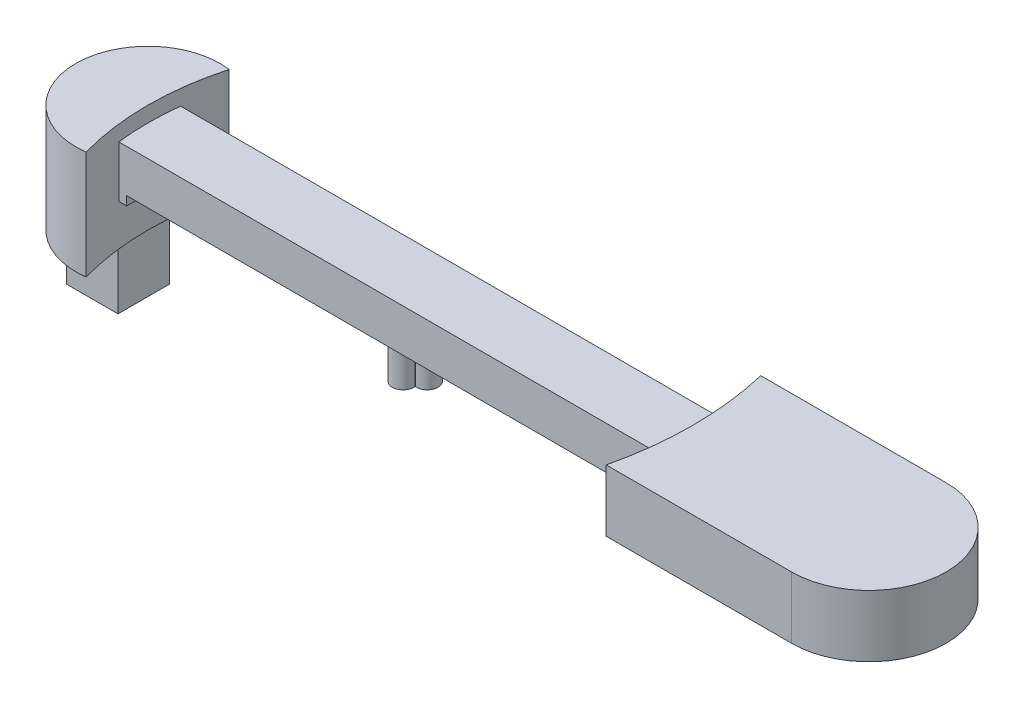
SolidWorks part; units mm, degrees
material "ABS"
ref_plane "Front Plane" through (0, 0, 0) normal (0, 0, 1) x (1, 0, 0)
ref_plane "Top Plane" through (0, 0, 0) normal (0, 1, 0) x (1, 0, 0)
ref_plane "Right Plane" through (0, 0, 0) normal (1, 0, 0) x (0, 0, -1)
sketch "Sketch1" plane through (0, 0, 0) normal (0, 1, 0) x (1, 0, 0)
  line L0 (0, -2241.9542) -> (0, 109855.7559) construction
  line L1 (0, 37.5) -> (90, 37.5)
  line L2 (0, -37.5) -> (90, -37.5)
  line L3 (-1077.9268, 34.7) -> (48922.0732, 34.7) construction
  line L4 (-1075.7317, -34.7) -> (48924.2683, -34.7) construction
  line L5 (0, 0) -> (-255.2, 0) construction
  line L6 (-263.8484, 15) -> (3.7007, 15)
  line L7 (-263.8484, -15) -> (3.7007, -15)
  arc A0 (90, -37.5) -> (90, 37.5) centre (90, 0) ccw
  arc A1 (0, -37.5) -> (0, 37.5) centre (-157.7468, 0) ccw
  arc A9 (-255.2, -34.7) -> (-255.2, 34.7) centre (-129.9167, 0) cw
  arc A10 (-255.2, 34.7) -> (-255.2, -34.7) centre (-259.9167, 0) ccw
  dimension "D8" = 130
  dimension "D9" = 15
  dimension "D1" = 90
  dimension "D2" = 90
  dimension "D3" = 37.5
  dimension "D4" = 37.5
  dimension "D5" = 34.7
  dimension "D6" = 34.7
  dimension "D7" = 255.2
  dimension "D10" = 15
extrude "Boss-Extrude1" add sketch "Sketch1" along normal blind 32.5 and the other way blind 20 contours A9 A10 region at (-273.8974, 0, 0)
extrude "Boss-Extrude2" add sketch "Sketch1<3>" along normal blind 30 separate body contours A1 L2 A0 L1 region at (61.4889, 0, 0)
sketch "Sketch1<3>" plane through (0, 0, 0) normal (0, 1, 0) x (1, 0, 0) same geometry as "Sketch1"
extrude "Boss-Extrude4" add sketch "Sketch1<5>" along normal blind 25 contours A9 L7 A1 L6 region at (-127.7316, 0, 0)
sketch "Sketch1<5>" plane through (0, 0, 0) normal (0, 1, 0) x (1, 0, 0) same geometry as "Sketch1"
sketch "Sketch2" plane through (0, -20, 0) normal (0, -1, 0) x (1, 0, 0)
  line L5 (-286.9307, -12.5) -> (-261.9307, -12.5)
  line L6 (-286.9307, -12.5) -> (-286.9307, 12.5)
  line L7 (-286.9307, 12.5) -> (-261.9307, 12.5)
  line L8 (-261.9307, -12.5) -> (-261.9307, 12.5)
  line L9 (-286.9307, -12.5) -> (-261.9307, 12.5) construction
  line L10 (-286.9307, 12.5) -> (-261.9307, -12.5) construction
  point P0 (-274.4307, 0)
  dimension "D1" = 25
  dimension "D2" = 25
extrude "Boss-Extrude5" add sketch "Sketch2" along normal blind 30
sketch "Sketch3" plane through (0, 0, 12.5) normal (0, 0, 1) x (1, 0, 0)
  line L0 (-286.9307, -50) -> (-286.9307, -20) construction
  line L1 (-261.9307, -50) -> (-286.9307, -50) construction
  circle A0 centre (-279.1307, -40) radius 2.5
  dimension "D3" = 5
  dimension "D1" = 7.8
  dimension "D2" = 10
extrude "Cut-Extrude1" cut sketch "Sketch3" against normal through all both and the other way through all
sketch "Sketch4" plane through (0, 0, 0) normal (0, -1, 0) x (1, 0, 0)
  line L1 (89.5, 15) -> (90.5, 15)
  line L2 (89.5, 15) -> (89.5, -15)
  line L3 (89.5, -15) -> (90.5, -15)
  line L4 (90.5, 15) -> (90.5, -15)
  line L5 (89.5, 15) -> (90.5, -15) construction
  line L6 (89.5, -15) -> (90.5, 15) construction
  arc A0 (90, -37.5) -> (90, 37.5) centre (90, 0) ccw construction
  point P0 (90, 0)
  dimension "D1" = 1
  dimension "D2" = 30
extrude "Boss-Extrude6" add sketch "Sketch4" along normal blind 15
sketch "Sketch5" plane through (90.5, 0, 0) normal (1, 0, 0) x (0, 0, -1)
  line L1 (-12.1494, -11.6013) -> (12.1494, -11.6013)
  line L2 (-12.1494, -11.6013) -> (-12.1494, -1.8817)
  line L3 (-12.1494, -1.8817) -> (12.1494, -1.8817)
  line L4 (12.1494, -11.6013) -> (12.1494, -1.8817)
  line L5 (-12.1494, -11.6013) -> (12.1494, -1.8817) construction
  line L6 (-12.1494, -1.8817) -> (12.1494, -11.6013) construction
  point P0 (0, -6.7415)
extrude "Cut-Extrude2" cut sketch "Sketch5" against normal blind 5 and the other way blind 2
sketch "Sketch6" plane through (0, 0, 15) normal (0, 0, 1) x (1, 0, 0)
  line L0 (-255.2, -20) -> (-255.2, 32.5) construction
  line L1 (-255.2, 4.3005) -> (3.7007, 4.3005)
  line L2 (-255.2, 4.3005) -> (-255.2, 0)
  line L3 (-255.2, 0) -> (3.7007, 0)
  line L4 (3.7007, 4.3005) -> (3.7007, 0)
extrude "Cut-Extrude3" cut sketch "Sketch6" against normal up to surface (30 mm away) up to face at (-127.6738, 12.5, -15)
sketch "Sketch7" plane through (0, 4.3005, 0) normal (0, -1, 0) x (1, 0, 0)
  line L0 (-255.2, -15) -> (-255.2, 15) construction
  line L1 (-132.7, 7.0711) -> (-132.7, -7.0711)
  line L2 (-127.7, 7.0711) -> (-127.7, -7.0711)
  line L3 (-124.8228, 5.2283) -> (-124.8228, -5.2283) construction
  arc A0 (-124.9717, -5.3772) -> (-124.8228, -5.2283) centre (-130.2, 0) ccw
  arc A1 (-127.7, 7.0711) -> (-132.7, 7.0711) centre (-130.2, 0) ccw
  arc A2 (-132.7, -7.0711) -> (-127.7, -7.0711) centre (-130.2, 0) ccw
  arc A3 (-135.4283, -5.3772) -> (-124.9717, -5.3772) centre (-130.2, -5.8539) ccw
  arc A4 (-135.5772, 5.2283) -> (-135.5772, -5.2283) centre (-136.0539, 0) ccw
  arc A5 (-124.9717, 5.3772) -> (-135.4283, 5.3772) centre (-130.2, 5.8539) ccw
  arc A6 (-124.8228, -5.2283) -> (-124.8228, 5.2283) centre (-124.3461, 0) ccw
  arc A7 (-135.5772, -5.2283) -> (-135.4283, -5.3772) centre (-130.2, 0) ccw
  arc A8 (-135.4283, 5.3772) -> (-135.5772, 5.2283) centre (-130.2, 0) ccw
  arc A9 (-124.8228, 5.2283) -> (-124.9717, 5.3772) centre (-130.2, 0) ccw
  dimension "D1" = 15
  dimension "D3" = 15
  dimension "D2" = 125
  dimension "D4" = 5
  dimension "D5" = 2.5
  dimension "D6" = 4
extrude "Boss-Extrude7" add sketch "Sketch7" along normal blind 20
